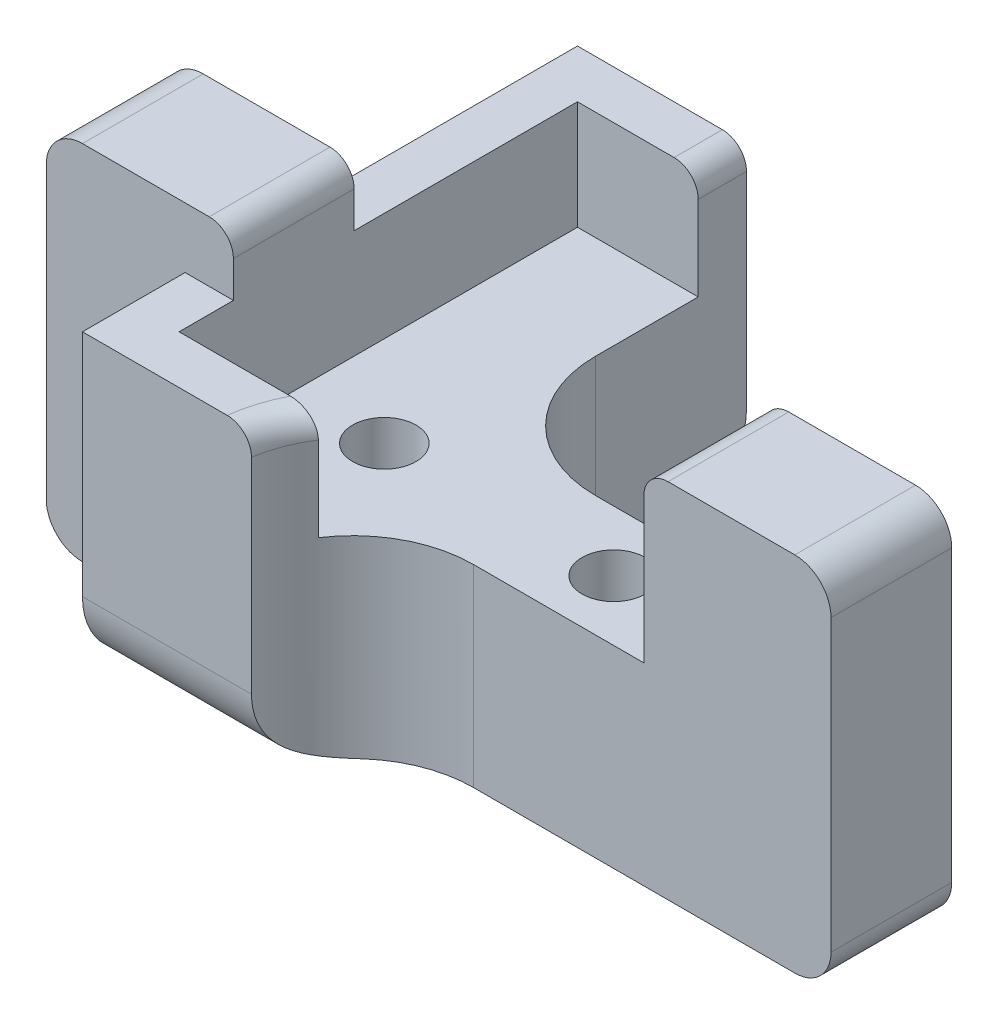
SolidWorks part; units mm, degrees
ref_plane "Front Plane" through (0, 0, 0) normal (0, 0, 1) x (1, 0, 0)
ref_plane "Top Plane" through (0, 0, 0) normal (0, 1, 0) x (1, 0, 0)
ref_plane "Right Plane" through (0, 0, 0) normal (1, 0, 0) x (0, 0, -1)
sketch "Sketch1" plane through (0, 0, 0) normal (0, 0, 1) x (1, 0, 0)
  line L5 (0, 0) -> (65, 0)
  line L6 (0, 0) -> (0, 30)
  line L7 (0, 30) -> (65, 30)
  line L8 (65, 0) -> (65, 30)
  dimension "D1" = 30
  dimension "D2" = 65
extrude "Boss-Extrude1" add sketch "Sketch1" along normal blind 10 contours L6 L5 L8 L7
sketch "Sketch2" plane through (0, 30, 0) normal (0, 1, 0) x (1, 0, 0)
  line L0 (0, 0) -> (65, 0) construction
  line L1 (15.5, 0) -> (49.5, 0)
  line L2 (15.5, 0) -> (15.5, -10)
  line L3 (15.5, -10) -> (49.5, -10)
  line L4 (49.5, 0) -> (49.5, -10)
  line L5 (0, -10) -> (65, -10) construction
  point P6 (32.5, 0)
  point P7 (32.5, 0)
  point P10 (32.5, -10)
  point P11 (32.5, -10)
  dimension "D1" = 34
extrude "Cut-Extrude1" cut sketch "Sketch2" against normal blind 14
sketch "Sketch4" plane through (0, 16, 0) normal (0, 1, 0) x (1, 0, 0)
  line L0 (23, -5) -> (42, -5) construction
  line L1 (49.5, 0) -> (15.5, 0) construction
  line L2 (0, -10) -> (0, 0) construction
  circle A0 centre (23, -5) radius 2.625
  circle A1 centre (42, -5) radius 2.625
  point P6 (32.5, 0)
  point P7 (32.5, -5)
  point P10 (0, -5)
  dimension "D2" = 5.25
  dimension "D1" = 19
extrude "Cut-Extrude3" cut sketch "Sketch4" against normal blind 45
fillet "Fillet1" radius 3 4 edges at (0, 30, 5) (65, 30, 5) (65, 0, 5) (0, 0, 5)
sketch "Sketch5" plane through (0, 16, 0) normal (0, 1, 0) x (1, 0, 0)
  line L0 (0, -10) -> (0, 0) construction
  line L1 (15.5, 18.5) -> (25.5, 18.5)
  line L2 (15.5, 18.5) -> (15.5, -14.5)
  line L3 (15.5, -14.5) -> (25.5, -14.5)
  line L4 (25.5, 18.5) -> (25.5, -14.5)
  circle A0 centre (23, -5) radius 2.625
  circle A3 centre (23, -5) radius 2.625 construction
  circle M5 centre (23, -5) radius 2.625
  line M7 (15.5, 0) -> (15.5, -10)
  line M8 (15.5, -10) -> (49.5, -10)
  line M10 (49.5, 0) -> (15.5, 0)
  dimension "D1" = 10
  dimension "D2" = 33
  dimension "D3" = 9.5
  dimension "D4" = 15.5
extrude "Boss-Extrude2" add sketch "Sketch5" against normal up to surface (16 mm away) contours L4 L2 L3 M8 | L4 M10 M7 M8 M5 | L4 L1 L2 M10 region at (20.5, 16, -9.25) region at (19.8191, 16, 5) region at (20.5, 16, 12.25) up to face at (23, 0, 7.625)
sketch "Sketch3" plane through (0, 0, 0) normal (0, -1, 0) x (1, 0, 0)
  line L0 (23, 5) -> (42, 5) construction
  line L1 (0, 10) -> (0, 0) construction
  line L2 (20.6184, 9.125) -> (18.2369, 5)
  line L3 (18.2369, 5) -> (20.6184, 0.875)
  line L4 (20.6184, 0.875) -> (25.3816, 0.875)
  line L5 (25.3816, 0.875) -> (27.7631, 5)
  line L6 (27.7631, 5) -> (25.3816, 9.125)
  line L7 (25.3816, 9.125) -> (20.6184, 9.125)
  line L8 (46.7631, 5) -> (44.3816, 9.125)
  line L9 (44.3816, 9.125) -> (39.6184, 9.125)
  line L10 (39.6184, 9.125) -> (37.2369, 5)
  line L11 (37.2369, 5) -> (39.6184, 0.875)
  line L12 (39.6184, 0.875) -> (44.3816, 0.875)
  line L13 (44.3816, 0.875) -> (46.7631, 5)
  line L14 (0, 10) -> (65, 10) construction
  circle A0 centre (23, 5) radius 4.125 construction
  circle A1 centre (42, 5) radius 4.125 construction
  point P18 (0, 5)
  point P21 (32.5, 10)
  point P22 (32.5, 5)
  dimension "D1" = 8.25
  dimension "D2" = 19
extrude "Cut-Extrude2" cut sketch "Sketch3" against normal blind 10
sketch "Sketch6" plane through (0, 0, 14.5) normal (0, 0, 1) x (1, 0, 0)
  line L1 (15.5, 0) -> (25.5, 0)
  line L2 (15.5, 0) -> (15.5, 25)
  line L3 (15.5, 25) -> (25.5, 25)
  line L4 (25.5, 0) -> (25.5, 25)
  dimension "D1" = 25
extrude "Boss-Extrude3" add sketch "Sketch6" along normal blind 4
extrude "Boss-Extrude4" add sketch "Sketch6<2>" against normal blind 4 from surface starting at face at (20.5, 8, -18.5)
sketch "Sketch6<2>" plane through (0, 0, 14.5) normal (0, 0, 1) x (1, 0, 0) same geometry as "Sketch6"
sketch "Sketch7" plane through (0, 0, 18.5) normal (0, 0, 1) x (1, 0, 0)
  line L0 (25.5, 25) -> (15.5, 25) construction
  line L1 (15.5, 25) -> (11.5, 25)
  line L2 (15.5, 25) -> (15.5, 0)
  line L3 (15.5, 0) -> (11.5, 0)
  line L4 (11.5, 25) -> (11.5, 0)
  line L5 (25.5, 0) -> (25.5, 25) construction
  line L6 (15.5, 25) -> (15.5, 0) construction
  line L7 (3, 0) -> (15.5, 0) construction
  dimension "D1" = 14
extrude "Boss-Extrude7" add sketch "Sketch7" against normal up to surface (41 mm away) up to face at (20.5, 12.5, -22.5)
fillet "Fillet2" radius 6 2 edges at (18.5, 0, -22.5) (18.5, 0, 18.5)
fillet "Fillet4" radius 10 2 edges at (25.5, 8, 0) (25.5, 8, 10)
fillet "Fillet7" radius 2 4 edges at (26.0509, 25, 16.4168) (25.5, 25, -20.5) (15.5, 30, 5) (49.5, 30, 5)
extrude "Boss-Extrude8" add sketch "Sketch3<2>" against normal offset from surface (4.75 mm away) 5.25 up to face at (42, 10, 5)
sketch "Sketch3<2>" plane through (0, 0, 0) normal (0, -1, 0) x (1, 0, 0) same geometry as "Sketch3"
